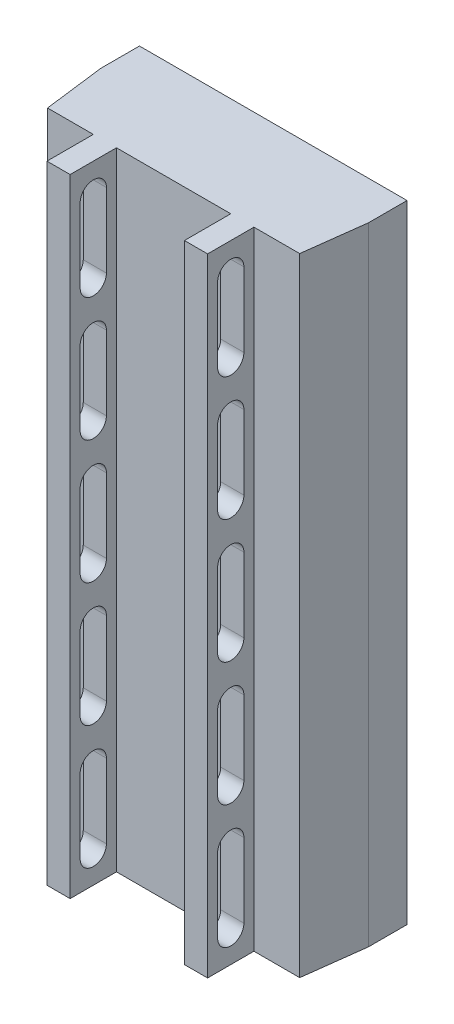
SolidWorks part; units mm, degrees
ref_plane "Front Plane" through (0, 0, 0) normal (0, 0, 1) x (1, 0, 0)
ref_plane "Top Plane" through (0, 0, 0) normal (0, 1, 0) x (1, 0, 0)
ref_plane "Right Plane" through (0, 0, 0) normal (1, 0, 0) x (0, 0, -1)
sketch "Sketch1" plane through (0, 0, 0) normal (0, 1, 0) x (1, 0, 0)
  line L0 (0, 0) -> (32.65, 0)
  line L1 (31.65, 1) -> (1, 1)
  line L2 (1, 1) -> (1, 15.9)
  line L3 (1, 15.9) -> (-1, 15.9)
  line L4 (-1, 15.9) -> (-1, 7.9)
  line L5 (-1, 7.9) -> (0, 0)
  line L6 (31.65, 1) -> (31.65, 15.9)
  line L7 (31.65, 15.9) -> (33.65, 15.9)
  line L8 (33.65, 15.9) -> (33.65, 7.9)
  line L9 (33.65, 7.9) -> (32.65, 0)
  point P3 (16.325, 1)
  point P7 (16.325, 1)
  dimension "D1" = 1
extrude "Boss-Extrude1" add sketch "Sketch1" along normal blind 80.2
sketch "Sketch2" plane through (0, 80.2, 0) normal (0, 1, 0) x (1, 0, 0)
  line L0 (32.65, 0) -> (0, 0)
  line L1 (0, 0) -> (-1, 7.9)
  line L2 (-1, 7.9) -> (-1, 15.9)
  line L3 (-1, 15.9) -> (33.65, 15.9)
  line L4 (33.65, 15.9) -> (33.65, 7.9)
  line L5 (33.65, 7.9) -> (32.65, 0)
extrude "Boss-Extrude2" add sketch "Sketch2" along normal blind 1
sketch "Sketch4" plane through (0, 0, 0) normal (0, 0, 1) x (1, 0, 0)
  line L0 (23.725, 81.2) -> (26.725, 81.2)
  line L2 (0, 81.2) -> (32.65, 81.2) construction
  line L3 (8.925, 81.2) -> (5.925, 81.2)
  line L4 (16.325, 0) -> (16.325, 81.2)
  line L5 (0, 0) -> (32.65, 0) construction
  line L6 (26.725, 81.2) -> (26.725, 0)
  line L7 (26.725, 0) -> (23.725, 0)
  line L8 (23.725, 0) -> (23.725, 81.2)
  line L9 (8.925, 81.2) -> (8.925, 0)
  line L10 (8.925, 0) -> (5.925, 0)
  line L11 (5.925, 0) -> (5.925, 81.2)
  point P5 (16.325, 81.2)
  point P6 (23.725, 81.2)
  point P7 (8.925, 81.2)
  line M5 (0, 0) -> (32.65, 0)
  line M7 (32.65, 81.2) -> (0, 81.2)
  dimension "D1" = 7.4
  dimension "D2" = 7.4
  dimension "D3" = 0
extrude "Boss-Extrude3" add sketch "Sketch4" along normal blind 6 contours L8 L6 M5 M7 | L11 L9 M5 M7 region at (25.225, 40.6, 0) region at (7.425, 40.6, 0)
hole_wizard "M3 Clearance Slot1" positions "Sketch20" profile "Sketch21" size "M3" standard "ANSI Metric" slot yes end condition through all
sketch "Sketch20" plane through (5.925, 0, 0) normal (-1, 0, 0) x (0, 0, 1)
  line L0 (3, 66.1) -> (3, 79.1) construction
  point P0 (3, 72.6)
  point P5 (3, 56.6)
  point P8 (3, 40.6)
  point P11 (3, 24.6)
  point P14 (3, 8.6)
  dimension "D1" = 13
sketch "Sketch21" plane through (5.925, 72.6, 3) normal (0, 1, 0) x (0, 0, 1)
  line L0 (0, 0) -> (0, 27.725)
  line L1 (0, 27.725) -> (1.7, 27.725)
  line L2 (1.7, 27.725) -> (1.7, 0)
  line L5 (1.7, 0) -> (0, 0)
  line L11 (0, -6.35) -> (0, 107.95) construction
  dimension "Thru Hole Dia." = 3.4
  dimension "Thru Hole Depth" = 27.725
sketch "Sketch22" plane through (5.925, 0, 0) normal (-1, 0, 0) x (0, 0, 1)
  arc A0 (1.3, 3.8) -> (4.7, 3.8) centre (3, 3.8) ccw construction
  point P0 (3, 2.1)
sketch "Sketch24" plane through (0, 81.2, 0) normal (0, 1, 0) x (1, 0, 0)
  line L0 (33.65, 15.9) -> (33.65, 12.9)
  line L1 (33.65, 7.9) -> (33.65, 15.9) construction
  line L4 (33.65, 15.9) -> (-1, 15.9) construction
  line L5 (26.45, 15.9) -> (33.65, 15.9)
  line L6 (-1, 15.9) -> (-1, 12.9)
  line L7 (-1, 15.9) -> (-1, 7.9) construction
  line L10 (6.2, 15.9) -> (-1, 15.9)
  line L11 (26.45, 12.9) -> (6.2, 12.9)
  line L12 (6.2, 15.9) -> (26.45, 15.9)
  line L13 (26.45, 12.9) -> (26.45, 15.9)
  line L14 (6.2, 12.9) -> (6.2, 15.9)
  line M7 (33.65, 15.9) -> (-1, 15.9)
extrude "Cut-Extrude5" cut sketch "Sketch24" against normal blind 1 contours L14 L11 L13 M7 region at (16.325, 81.2, -14.4)
sketch "Sketch30" plane through (0, 0, -1) normal (0, 0, -1) x (-1, 0, 0)
  line L0 (-31.65, 0) -> (-1, 0) construction
  line L1 (-1, 80.2) -> (-1, 0) construction
  line L6 (-31.65, 14.3907) -> (-1, 14.3907)
  line L8 (-31.65, 80.2) -> (-1, 80.2) construction
  line L9 (-31.65, 80.2) -> (-31.65, 0) construction
  line L10 (-26.8, 64.95) -> (-5.8, 64.95)
  line L11 (-26.8, 64.95) -> (-26.8, 27.95)
  line L12 (-26.8, 27.95) -> (-5.8, 27.95)
  line L13 (-5.8, 64.95) -> (-5.8, 27.95)
  line L14 (-16.3, 27.95) -> (-13.175, 27.95)
  line L15 (-6.8, 63.95) -> (-25.8, 63.95)
  line L16 (-6.8, 63.95) -> (-6.8, 28.95)
  line L17 (-6.8, 28.95) -> (-25.8, 28.95)
  line L18 (-25.8, 63.95) -> (-25.8, 28.95)
  line L19 (-13.175, 28.95) -> (-16.3, 28.95)
  line L20 (-16.3, 28.95) -> (-19.425, 28.95)
  line L21 (-19.425, 28.95) -> (-19.425, 27.95)
  line L22 (-19.425, 27.95) -> (-16.3, 27.95)
  line L23 (-13.175, 28.95) -> (-13.175, 27.95)
  line L24 (-31.65, 27.95) -> (-1, 27.95)
  line L25 (-19.425, 27.95) -> (-19.425, 14.3907)
  line L26 (-19.425, 14.3907) -> (-13.175, 14.3907)
  line L27 (-13.175, 14.3907) -> (-13.175, 28.95)
  point P0 (-16.3, 46.45)
  point P5 (-26.8, 46.45)
  point P6 (-5.8, 46.45)
  point P7 (-16.3, 64.95)
  point P8 (-16.3, 27.95)
  line M6 (-1, 0) -> (-1, 80.2)
  line M7 (-1, 80.2) -> (-31.65, 80.2)
  line M8 (-31.65, 80.2) -> (-31.65, 0)
  dimension "D1" = 46.45
  dimension "D2" = 15.3
  dimension "D3" = 15.3
  dimension "D4" = 10.5
  dimension "D5" = 10.5
  dimension "D6" = 33.75
  dimension "D7" = 18.5
  dimension "D8" = 18.5
  dimension "D9" = 4.8
  dimension "D10" = 4.85
  dimension "D11" = 15.25
  dimension "D12" = 27.95
  dimension "D13" = 1
  dimension "D14" = 1
  dimension "D15" = 1
  dimension "D16" = 1
  dimension "D17" = 6.25
extrude "Boss-Extrude7" add sketch "Sketch30" along normal blind 7.8 contours L17 L23 L12 L13 L10 L11 L21 L18 L15 L16 | L24 L11 L10 L13 M8 M6 M7 | L25 L12 L24 L6 M8 | L27 L6 L24 L12 M6 region at (25.5375, 21.1703, -1) region at (31.0442, 54.075, -1) region at (7.0875, 21.1703, -1) region at (23.1125, 28.3754, -1)
sketch "Sketch31" plane through (0, 0, 0) normal (0, -1, 0) x (1, 0, 0)
  line L0 (33.65, -15.9) -> (33.65, -12.9)
  line L1 (33.65, -7.9) -> (33.65, -15.9) construction
  line L2 (33.65, -12.9) -> (-1, -12.9)
  line L3 (-1, -15.9) -> (-1, -7.9) construction
  line L4 (-1, -12.9) -> (-1, -15.9)
  line L5 (-1, -15.9) -> (33.65, -15.9)
extrude "Cut-Extrude6" cut sketch "Sketch31" against normal blind 95
sketch "Sketch32" plane through (0, 0, -1) normal (0, 0, -1) x (-1, 0, 0)
  line L0 (-31.65, 0) -> (-1, 0) construction
  point P0 (-16.325, 0)
sketch "Sketch33" plane through (0, 0, -8.8) normal (0, 0, -1) x (-1, 0, 0)
  line L0 (-1, 80.2) -> (-31.65, 80.2) construction
  point P0 (-16.325, 80.2)
sketch "Sketch34" plane through (0, 0, -1) normal (0, 0, -1) x (-1, 0, 0)
  line L1 (-19.425, 14.3907) -> (-13.175, 14.3907)
  line L2 (-19.425, 14.3907) -> (-19.425, 28.95)
  line L3 (-19.425, 28.95) -> (-13.175, 28.95)
  line L4 (-13.175, 14.3907) -> (-13.175, 28.95)
extrude "Boss-Extrude8" add sketch "Sketch34" along normal blind 7.6
sketch "Sketch35" plane through (0, 0, -8.8) normal (0, 0, -1) x (-1, 0, 0)
  line L0 (-31.65, 0) -> (-1, 0) construction
  line L1 (-31.65, 80.2) -> (-31.65, 14.3907) construction
  line L2 (-1, 14.3907) -> (-1, 80.2) construction
  circle A0 centre (-26.475, 70.1) radius 2.1
  circle A1 centre (-6.175, 70.1) radius 2.1
  circle A2 centre (-6.175, 17.95) radius 2.1
  circle A3 centre (-26.475, 17.95) radius 2.1
  point P0 (-26.475, 17.95)
  point P5 (-6.175, 17.95)
  point P8 (-26.475, 70.1)
  point P9 (-6.175, 70.1)
  dimension "D5" = 70.1
  dimension "D1" = 17.95
  dimension "D2" = 5.175
  dimension "D3" = 5.175
  dimension "D4" = 70.1
extrude "Cut-Extrude7" cut sketch "Sketch35" against normal blind 4
sketch "Sketch36" plane through (0, 0, -1) normal (0, 0, -1) x (-1, 0, 0)
  line L1 (-25.8, 63.95) -> (-6.8, 63.95)
  line L2 (-25.8, 63.95) -> (-25.8, 28.95)
  line L3 (-25.8, 28.95) -> (-6.8, 28.95)
  line L4 (-6.8, 63.95) -> (-6.8, 28.95)
extrude "Boss-Extrude9" add sketch "Sketch36" along normal blind 0.8
sketch "Sketch37" plane through (0, 0, -8.8) normal (0, 0, -1) x (-1, 0, 0)
  line L0 (-31.65, 80.2) -> (-31.65, 14.3907) construction
  line L1 (-1, 80.2) -> (-31.65, 80.2) construction
  line L2 (-1, 14.3907) -> (-1, 80.2) construction
  point P0 (-28.15, 76.7)
  point P1 (-4.5, 76.7)
  dimension "D1" = 3.5
  dimension "D2" = 3.5
  dimension "D3" = 3.5
  dimension "D4" = 3.5
hole_wizard "Tap Drill for M3x0.5 Tap1" positions "3DSketch1" profile "Sketch38" hole size "M3x0.5" standard "ANSI Metric"
sketch3d "3DSketch1"
  point P0 (28.15, 76.7, -8.8)
  point P3 (4.5, 76.7, -8.8)
sketch "Sketch38" plane through (28.15, 76.7, -8.8) normal (1, 0, 0) x (0, 1, 0)
  line L0 (0, 0) -> (0, 7.2511)
  line L1 (0, 7.2511) -> (1.25, 6.5)
  line L2 (1.25, 6.5) -> (1.25, 0)
  line L5 (1.25, 0) -> (0, 0)
  line L10 (0, 7.2511) -> (-1.25, 6.5) construction
  line L11 (0, -6.35) -> (0, 107.95) construction
  dimension "Hole Dia." = 2.5
  dimension "Hole Depth" = 6.5
  dimension "Drill Angle" = 118
sketch "Sketch39" plane through (0, 0, -8.8) normal (0, 0, -1) x (-1, 0, 0)
  circle A0 centre (-28.15, 76.7) radius 3.18
sketch "Sketch40" plane through (0, 0, -1) normal (0, 0, -1) x (-1, 0, 0)
  point P0 (-21.2112, 6.1163)
sketch "Sketch43" plane through (0, 0, -8.8) normal (0, 0, -1) x (-1, 0, 0)
  line L0 (-31.65, 80.2) -> (-31.65, 14.3907) construction
  line L1 (-31.65, 0) -> (-1, 0) construction
  line L2 (-1, 14.3907) -> (-1, 80.2) construction
  point P0 (-25.725, 22.85)
  point P5 (-6.925, 22.85)
  dimension "D1" = 5.925
  dimension "D2" = 22.85
  dimension "D3" = 5.925
hole_wizard "Tap Drill for M3x0.5 Tap2" positions "3DSketch3" profile "Sketch44" hole size "M3x0.5" standard "ANSI Metric"
sketch3d "3DSketch3"
  point P0 (25.725, 22.85, -8.8)
  point P3 (6.925, 22.85, -8.8)
sketch "Sketch44" plane through (25.725, 22.85, -8.8) normal (1, 0, 0) x (0, 1, 0)
  line L0 (0, 0) -> (0, 7.2511)
  line L1 (0, 7.2511) -> (1.25, 6.5)
  line L2 (1.25, 6.5) -> (1.25, 0)
  line L5 (1.25, 0) -> (0, 0)
  line L10 (0, 7.2511) -> (-1.25, 6.5) construction
  line L11 (0, -6.35) -> (0, 107.95) construction
  dimension "Hole Dia." = 2.5
  dimension "Hole Depth" = 6.5
  dimension "Drill Angle" = 118
